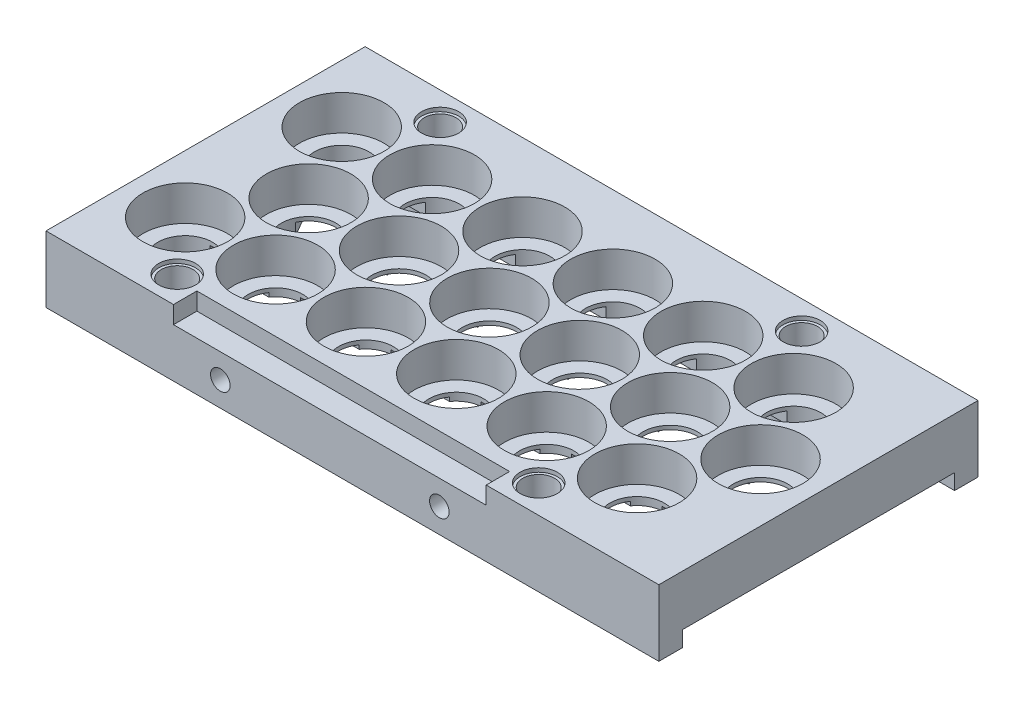
SolidWorks part; units mm, degrees
ref_plane "Front Plane" through (0, 0, 0) normal (0, 0, 1) x (1, 0, 0)
ref_plane "Top Plane" through (0, 0, 0) normal (0, 1, 0) x (1, 0, 0)
ref_plane "Right Plane" through (0, 0, 0) normal (1, 0, 0) x (0, 0, -1)
sketch "Sketch1" plane through (0, 0, 0) normal (0, 1, 0) x (1, 0, 0)
  line L0 (0, 0) -> (11.575, -20.0485) construction
  line L1 (11.575, -20.0485) -> (0, -40.097) construction
  line L2 (0, 0) -> (11.575, 0) construction
  line L3 (11.575, 0) -> (11.575, -20.0485) construction
  line L4 (11.575, -20.0485) -> (11.575, -40.097) construction
  line L5 (11.575, -40.097) -> (0, -40.097) construction
  line L6 (0, 0) -> (23.15, 0) construction
  line L7 (0, 0) -> (23.15, 0) construction
  line L8 (-14.825, -60.922) -> (142.15, -60.922)
  line L9 (-14.825, -60.922) -> (-14.825, 20.825)
  line L10 (-14.825, 20.825) -> (142.15, 20.825)
  line L11 (142.15, -60.922) -> (142.15, 20.825)
  circle A0 centre (0, 0) radius 10.825
  circle A1 centre (11.575, -20.0485) radius 10.825
  circle A2 centre (0, -40.097) radius 10.825
  circle A3 centre (23.15, 0) radius 10.825
  circle A4 centre (34.725, -20.0485) radius 10.825
  circle A5 centre (23.15, -40.097) radius 10.825
  circle A6 centre (46.3, 0) radius 10.825
  circle A7 centre (57.875, -20.0485) radius 10.825
  circle A8 centre (46.3, -40.097) radius 10.825
  circle A9 centre (69.45, 0) radius 10.825
  circle A10 centre (81.025, -20.0485) radius 10.825
  circle A11 centre (69.45, -40.097) radius 10.825
  circle A12 centre (92.6, 0) radius 10.825
  circle A13 centre (104.175, -20.0485) radius 10.825
  circle A14 centre (92.6, -40.097) radius 10.825
  circle A15 centre (115.75, 0) radius 10.825
  circle A16 centre (127.325, -20.0485) radius 10.825
  circle A17 centre (115.75, -40.097) radius 10.825
  circle A18 centre (0, 0) radius 7
  circle A19 centre (11.575, -20.0485) radius 7
  circle A20 centre (0, -40.097) radius 7
  circle A21 centre (23.15, 0) radius 7
  circle A22 centre (34.725, -20.0485) radius 7
  circle A23 centre (23.15, -40.097) radius 7
  circle A24 centre (46.3, 0) radius 7
  circle A25 centre (57.875, -20.0485) radius 7
  circle A26 centre (46.3, -40.097) radius 7
  circle A27 centre (69.45, 0) radius 7
  circle A28 centre (81.025, -20.0485) radius 7
  circle A29 centre (69.45, -40.097) radius 7
  circle A30 centre (92.6, 0) radius 7
  circle A31 centre (104.175, -20.0485) radius 7
  circle A32 centre (92.6, -40.097) radius 7
  circle A33 centre (115.75, 0) radius 7
  circle A34 centre (127.325, -20.0485) radius 7
  circle A35 centre (115.75, -40.097) radius 7
  dimension "D3" = 21.65
  dimension "D11" = 14
  dimension "D1" = 60
  dimension "D2" = 60
  dimension "D4" = 1.5
  dimension "D6" = 23.15
  dimension "D7" = 4
  dimension "D8" = 4
  dimension "D9" = 10
  dimension "D10" = 10
  dimension "D13" = 23.15
  dimension "D5" = 6
  dimension "D12" = 6
extrude "Boss-Extrude2" add sketch "Sketch1" along normal blind 11 contours L8 L11 L10 L9 A17 A16 A15 A14 A13 A12 A11 A10 A9 A8 A7 A6 A5 A4 A3 A2 A1 A0 region at (-13.0551, 0, 20.0485)
extrude "Boss-Extrude3" add sketch "Sketch1<3>" along normal blind 2 contours A0 A18 | A3 A21 | A6 A24 | A9 A27 | A12 A30 | A15 A33 | A1 A19 | A4 A22 | A7 A25 | A10 A28 | A13 A31 | A16 A34 | A17 A35 | A14 A32 | A11 A29 | A8 A26 | A5 A23 | A2 A20 region at (-10.5188, 0, 0) region at (1.0562, 0, 20.0485) region at (-10.5188, 0, 40.097) region at (12.6312, 0, 0) region at (24.2062, 0, 20.0485) region at (12.6312, 0, 40.097) region at (35.7812, 0, 0) region at (47.3562, 0, 20.0485) region at (35.7812, 0, 40.097) region at (58.9312, 0, 0) region at (70.5062, 0, 20.0485) region at (58.9312, 0, 40.097) region at (82.0812, 0, 0) region at (93.6562, 0, 20.0485) region at (82.0812, 0, 40.097) region at (105.2312, 0, 0) region at (116.8062, 0, 20.0485) region at (105.2312, 0, 40.097)
sketch "Sketch1<3>" plane through (0, 0, 0) normal (0, 1, 0) x (1, 0, 0) same geometry as "Sketch1"
sketch "Sketch2" plane through (0, 0, 0) normal (0, -1, 0) x (1, 0, 0)
  line L0 (0, 40.097) -> (11.575, 20.0485) construction
  line L1 (3.4641, 42.097) -> (15.0391, 22.0485)
  line L2 (-3.4641, 38.097) -> (8.1109, 18.0485)
  line L3 (11.575, 20.0485) -> (0, 0) construction
  line L4 (15.0391, 18.0485) -> (3.4641, -2)
  line L5 (8.1109, 22.0485) -> (-3.4641, 2)
  line L6 (19.6859, 38.097) -> (31.2609, 18.0485)
  line L7 (26.6141, 42.097) -> (38.1891, 22.0485)
  line L8 (31.2609, 22.0485) -> (19.6859, 2)
  line L9 (38.1891, 18.0485) -> (26.6141, -2)
  line L10 (23.15, 40.097) -> (34.725, 20.0485) construction
  line L11 (34.725, 20.0485) -> (23.15, 0) construction
  line L12 (42.8359, 38.097) -> (54.4109, 18.0485)
  line L13 (49.7641, 42.097) -> (61.3391, 22.0485)
  line L14 (54.4109, 22.0485) -> (42.8359, 2)
  line L15 (61.3391, 18.0485) -> (49.7641, -2)
  line L16 (46.3, 40.097) -> (57.875, 20.0485) construction
  line L17 (57.875, 20.0485) -> (46.3, 0) construction
  line L18 (65.9859, 38.097) -> (77.5609, 18.0485)
  line L19 (72.9141, 42.097) -> (84.4891, 22.0485)
  line L20 (77.5609, 22.0485) -> (65.9859, 2)
  line L21 (84.4891, 18.0485) -> (72.9141, -2)
  line L22 (69.45, 40.097) -> (81.025, 20.0485) construction
  line L23 (81.025, 20.0485) -> (69.45, 0) construction
  line L24 (89.1359, 38.097) -> (100.7109, 18.0485)
  line L25 (96.0641, 42.097) -> (107.6391, 22.0485)
  line L26 (100.7109, 22.0485) -> (89.1359, 2)
  line L27 (107.6391, 18.0485) -> (96.0641, -2)
  line L28 (92.6, 40.097) -> (104.175, 20.0485) construction
  line L29 (104.175, 20.0485) -> (92.6, 0) construction
  line L30 (112.2859, 38.097) -> (123.8609, 18.0485)
  line L31 (119.2141, 42.097) -> (130.7891, 22.0485)
  line L32 (123.8609, 22.0485) -> (112.2859, 2)
  line L33 (130.7891, 18.0485) -> (119.2141, -2)
  line L34 (115.75, 40.097) -> (127.325, 20.0485) construction
  line L35 (127.325, 20.0485) -> (115.75, 0) construction
  line L36 (-3.4641, 38.097) -> (19.6859, 38.097) construction
  line L37 (0, 40.097) -> (115.75, 40.097) construction
  line L38 (0, 44.097) -> (115.75, 44.097)
  line L39 (0, 36.097) -> (115.75, 36.097)
  line L40 (11.575, 20.0485) -> (127.325, 20.0485) construction
  line L41 (11.575, 24.0485) -> (127.325, 24.0485)
  line L42 (11.575, 16.0485) -> (127.325, 16.0485)
  line L43 (0, 0) -> (115.75, 0) construction
  line L44 (0, 4) -> (115.75, 4)
  line L45 (0, -4) -> (115.75, -4)
  arc A0 (3.4641, 42.097) -> (-3.4641, 38.097) centre (0, 40.097) ccw
  arc A1 (8.1109, 18.0485) -> (15.0391, 22.0485) centre (11.575, 20.0485) ccw
  arc A2 (15.0391, 18.0485) -> (8.1109, 22.0485) centre (11.575, 20.0485) ccw
  arc A3 (-3.4641, 2) -> (3.4641, -2) centre (0, 0) ccw
  arc A4 (26.6141, 42.097) -> (19.6859, 38.097) centre (23.15, 40.097) ccw
  arc A5 (31.2609, 18.0485) -> (38.1891, 22.0485) centre (34.725, 20.0485) ccw
  arc A6 (38.1891, 18.0485) -> (31.2609, 22.0485) centre (34.725, 20.0485) ccw
  arc A7 (19.6859, 2) -> (26.6141, -2) centre (23.15, 0) ccw
  arc A8 (49.7641, 42.097) -> (42.8359, 38.097) centre (46.3, 40.097) ccw
  arc A9 (54.4109, 18.0485) -> (61.3391, 22.0485) centre (57.875, 20.0485) ccw
  arc A10 (61.3391, 18.0485) -> (54.4109, 22.0485) centre (57.875, 20.0485) ccw
  arc A11 (42.8359, 2) -> (49.7641, -2) centre (46.3, 0) ccw
  arc A12 (72.9141, 42.097) -> (65.9859, 38.097) centre (69.45, 40.097) ccw
  arc A13 (77.5609, 18.0485) -> (84.4891, 22.0485) centre (81.025, 20.0485) ccw
  arc A14 (84.4891, 18.0485) -> (77.5609, 22.0485) centre (81.025, 20.0485) ccw
  arc A15 (65.9859, 2) -> (72.9141, -2) centre (69.45, 0) ccw
  arc A16 (96.0641, 42.097) -> (89.1359, 38.097) centre (92.6, 40.097) ccw
  arc A17 (100.7109, 18.0485) -> (107.6391, 22.0485) centre (104.175, 20.0485) ccw
  arc A18 (107.6391, 18.0485) -> (100.7109, 22.0485) centre (104.175, 20.0485) ccw
  arc A19 (89.1359, 2) -> (96.0641, -2) centre (92.6, 0) ccw
  arc A20 (119.2141, 42.097) -> (112.2859, 38.097) centre (115.75, 40.097) ccw
  arc A21 (123.8609, 18.0485) -> (130.7891, 22.0485) centre (127.325, 20.0485) ccw
  arc A22 (130.7891, 18.0485) -> (123.8609, 22.0485) centre (127.325, 20.0485) ccw
  arc A23 (112.2859, 2) -> (119.2141, -2) centre (115.75, 0) ccw
  arc A24 (0, 44.097) -> (0, 36.097) centre (0, 40.097) ccw
  arc A25 (115.75, 36.097) -> (115.75, 44.097) centre (115.75, 40.097) ccw
  arc A26 (11.575, 24.0485) -> (11.575, 16.0485) centre (11.575, 20.0485) ccw
  arc A27 (127.325, 16.0485) -> (127.325, 24.0485) centre (127.325, 20.0485) ccw
  arc A28 (0, 4) -> (0, -4) centre (0, 0) ccw
  arc A29 (115.75, -4) -> (115.75, 4) centre (115.75, 0) ccw
  point P3 (5.7875, 30.0727)
  point P8 (5.7875, 10.0242)
  point P18 (28.9375, 30.0727)
  point P25 (28.9375, 10.0242)
  point P34 (52.0875, 30.0727)
  point P39 (52.0875, 10.0242)
  point P48 (75.2375, 30.0727)
  point P53 (75.2375, 10.0242)
  point P62 (98.3875, 30.0727)
  point P67 (98.3875, 10.0242)
  point P76 (121.5375, 30.0727)
  point P81 (121.5375, 10.0242)
  point P91 (57.875, 40.097)
  point P96 (69.45, 20.0485)
  point P103 (57.875, 0)
  circle M62 centre (0, 0) radius 7
  circle M63 centre (23.15, 0) radius 7
  circle M64 centre (46.3, 0) radius 7
  circle M65 centre (69.45, 0) radius 7
  circle M66 centre (92.6, 0) radius 7
  circle M67 centre (115.75, 0) radius 7
  circle M68 centre (11.575, 20.0485) radius 7
  circle M69 centre (34.725, 20.0485) radius 7
  circle M70 centre (57.875, 20.0485) radius 7
  circle M71 centre (81.025, 20.0485) radius 7
  circle M72 centre (104.175, 20.0485) radius 7
  circle M73 centre (127.325, 20.0485) radius 7
  circle M74 centre (115.75, 40.097) radius 7
  circle M75 centre (92.6, 40.097) radius 7
  circle M76 centre (69.45, 40.097) radius 7
  circle M77 centre (46.3, 40.097) radius 7
  circle M78 centre (23.15, 40.097) radius 7
  circle M79 centre (0, 40.097) radius 7
  dimension "D1" = 8
  dimension "D3" = 23.15
  dimension "D4" = 8
  dimension "D5" = 8
  dimension "D6" = 8
extrude "Cut-Extrude1" cut sketch "Sketch2" against normal blind 1 contours L1 L39 L38 M78 M79 | L7 L39 L38 M77 M78 | L39 L2 L1 M79 M68 | L42 L8 L6 L41 M68 M69 | L6 L41 L7 L39 M69 M78 | L12 L41 L13 L39 M70 M77 | L13 L39 L38 M76 M77 | L18 L41 L19 L39 M71 M76 | L19 L39 L38 M75 M76 | L24 L41 L25 L39 M72 M75 | L25 L39 L38 M74 M75 | L30 L41 L31 M73 M74 | L42 L32 L30 L41 M72 M73 | L42 L26 L24 L41 M71 M72 | L42 L20 L18 L41 M70 M71 | L42 L14 L12 L41 M69 M70 | L45 L44 L4 M62 M63 | L44 L4 L5 M62 M68 | L45 L44 L9 M63 M64 | L45 L44 L15 M64 M65 | L45 L44 L21 M65 M66 | L45 L44 L27 M66 M67 | L44 L27 L42 L26 M66 M72 | L42 L32 L33 M67 M73 | L44 L21 L42 L20 M65 M71 | L44 L15 L42 L14 M64 M70 | L39 L13 M77 | L39 L25 M75 | L39 L19 M76 | L41 L6 M69 | L44 L4 M62 | L44 L15 M64 | L44 L21 M65 | L44 L27 M66 | L41 L30 M73 | L32 L42 M73 | L41 L24 M72 | L26 L42 M72 | L41 L18 M71 | L20 L42 M71 | L41 L12 M70 | L14 L42 M70 | L44 L9 L42 L8 M63 M69 | L8 L42 M69 | L39 L7 M78 | L39 L1 M79 | L44 A29 L45 A28 region at (11.6138, 0, 40.1242) region at (6.3461, 0, 36.4331) region at (5.7834, 0, 30.0255) region at (23.0718, 0, 20.0485) region at (28.9375, 0, 30.0727) region at (34.7638, 0, 40.1242) region at (28.3789, 0, 23.7124) region at (5.7834, 0, 10.0715) region at (29.4961, 0, 36.4331) region at (57.9138, 0, 40.1242) region at (28.3789, 0, 16.3846) region at (28.9375, 0, 10.0242) region at (6.3461, 0, 3.6639) region at (11.6138, 0, -0.0272) region at (52.0875, 0, 30.0727) region at (46.2218, 0, 20.0485) region at (52.6461, 0, 36.4331) region at (81.0638, 0, 40.1242) region at (51.5289, 0, 23.7124) region at (34.7638, 0, -0.0272) region at (75.2375, 0, 30.0727) region at (75.7961, 0, 36.4331) region at (104.2138, 0, 40.1242) region at (74.6789, 0, 23.7124) region at (69.3718, 0, 20.0485) region at (51.5289, 0, 16.3846) region at (52.0875, 0, 10.0242) region at (57.9138, 0, -0.0272) region at (98.3875, 0, 30.0727) region at (98.9461, 0, 36.4331) region at (97.8289, 0, 23.7124) region at (92.5218, 0, 20.0485) region at (74.6789, 0, 16.3846) region at (52.6461, 0, 3.6639) region at (81.0638, 0, -0.0272) region at (121.5416, 0, 30.12) region at (75.2375, 0, 10.0242) region at (120.9789, 0, 23.7124) region at (115.6718, 0, 20.0485) region at (97.8289, 0, 16.3846) region at (75.7961, 0, 3.6639) region at (104.2138, 0, -0.0272) region at (98.3875, 0, 10.0242) region at (121.5416, 0, 9.977) region at (120.9789, 0, 16.3846) region at (98.9461, 0, 3.6639)
sketch "Sketch9" plane through (0, 11, 0) normal (0, 1, 0) x (1, 0, 0)
  line L0 (11.575, -60.922) -> (11.575, 20.825)
  line L1 (-14.825, 20.825) -> (142.15, 20.825) construction
  line L2 (104.175, 20.825) -> (104.175, -60.922)
  line L3 (-14.825, -60.922) -> (142.15, -60.922) construction
  circle A0 centre (11.575, 13.625) radius 4.0767
  circle A1 centre (11.575, -53.722) radius 4.0767
  circle A2 centre (104.175, -53.722) radius 4.0767
  circle A3 centre (104.175, 13.625) radius 4.0767
  point P0 (11.575, 13.625)
  point P7 (11.575, -20.0485)
  point P15 (104.175, -20.0485)
  point P20 (104.175, 13.625)
  point P21 (104.175, -53.722)
  point P22 (11.575, -53.722)
  dimension "D5" = 8.1534
  dimension "D1" = 7.2
  dimension "D4" = 7.2
extrude "Cut-Extrude3" cut sketch "Sketch9" against normal up to next contours A2 | A1 | A0 | A3
sketch "Sketch10" plane through (0, 11, 0) normal (0, 1, 0) x (1, 0, 0)
  circle A0 centre (11.575, 13.625) radius 4.7625
  circle A1 centre (104.175, 13.625) radius 4.7625
  circle A2 centre (104.175, -53.722) radius 4.7625
  circle A3 centre (11.575, -53.722) radius 4.7625
  dimension "D1" = 9.525
extrude "Cut-Extrude4" cut sketch "Sketch10" against normal blind 1
sketch "Sketch13" plane through (0, 0, 0) normal (0, -1, 0) x (1, 0, 0)
  line L0 (142.15, 60.922) -> (142.15, -20.825) construction
  line L5 (3.575, 53.722) -> (3.575, 60.922)
  line L8 (-14.825, 60.922) -> (142.15, 60.922) construction
  line L9 (3.575, 60.922) -> (19.575, 60.922)
  line L10 (19.575, 60.922) -> (19.575, 53.722)
  line L12 (57.875, 20.0485) -> (57.875, -20.825) construction
  line L13 (-14.825, -20.825) -> (142.15, -20.825) construction
  line L14 (11.575, 20.0485) -> (127.325, 20.0485) construction
  line L16 (96.175, 60.922) -> (96.175, 53.722)
  line L17 (112.175, 60.922) -> (96.175, 60.922)
  line L18 (112.175, 53.722) -> (112.175, 60.922)
  line L19 (-14.825, 60.922) -> (142.15, 60.922)
  line L20 (-14.825, 60.922) -> (-14.825, 54.922)
  line L21 (-14.825, 54.922) -> (142.15, 54.922)
  line L22 (142.15, 60.922) -> (142.15, 54.922)
  line L23 (142.15, -20.825) -> (142.15, -14.825)
  line L24 (-14.825, -14.825) -> (142.15, -14.825)
  line L25 (-14.825, -20.825) -> (-14.825, -14.825)
  line L26 (-14.825, -20.825) -> (142.15, -20.825)
  line L27 (112.175, -13.625) -> (112.175, -20.825)
  line L28 (112.175, -20.825) -> (96.175, -20.825)
  line L29 (96.175, -20.825) -> (96.175, -13.625)
  line L32 (19.575, -20.825) -> (19.575, -13.625)
  line L33 (3.575, -20.825) -> (19.575, -20.825)
  line L34 (3.575, -13.625) -> (3.575, -20.825)
  circle A4 centre (11.575, 53.722) radius 6.5
  circle A5 centre (11.575, 53.722) radius 8
  circle A6 centre (104.175, 53.722) radius 8
  circle A7 centre (104.175, 53.722) radius 6.5
  circle A8 centre (104.175, -13.625) radius 6.5
  circle A9 centre (104.175, -13.625) radius 8
  circle A10 centre (11.575, -13.625) radius 8
  circle A11 centre (11.575, -13.625) radius 6.5
  line M15 (142.15, 60.922) -> (-14.825, 60.922)
  line M16 (-14.825, 60.922) -> (-14.825, -20.825)
  line M17 (-14.825, -20.825) -> (142.15, -20.825)
  line M18 (142.15, -20.825) -> (142.15, 60.922)
  dimension "D1" = 13
  dimension "D2" = 16
  dimension "D3" = 6
extrude "Boss-Extrude7" add sketch "Sketch13" along normal blind 6 contours L21 L5 M16 M15 | A5 L5 L21 M15 | A5 L21 L10 M15 | L10 L21 L16 M15 | L21 A5 L19 A4 | A5 L21 A4 | L21 A6 L16 M15 | L21 A7 A6 L19 | L21 A7 A6 | A6 L21 L18 M15 | L18 L21 M18 M15 | A9 L24 L29 L26 | L28 A9 L24 A8 | A9 L26 L27 L24 | L24 L27 L26 M18 | L32 L26 L29 L24 | L24 A9 A8 | L34 L24 M16 M17 | L26 A10 L24 L34 | L24 A11 A10 | L24 A11 A10 L33 | L24 A10 L26 L32 region at (3.7817, 0, 54.3098) region at (-5.625, 0, 57.922) region at (4.8282, 0, 59.2567) region at (5.2714, 0, 58.3681) region at (18.3218, 0, 59.2567) region at (57.875, 0, 57.922) region at (-5.625, 0, -17.825) region at (97.4282, 0, 59.2567) region at (4.8282, 0, -19.1597) region at (96.3817, 0, 54.3098) region at (97.8714, 0, 58.3681) region at (3.7817, 0, -14.2128) region at (4.4261, 0, -14.9942) region at (110.9218, 0, 59.2567) region at (127.1625, 0, 57.922) region at (18.3218, 0, -19.1597) region at (57.875, 0, -17.825) region at (97.4282, 0, -19.1597) region at (127.1625, 0, -17.825) region at (96.3817, 0, -14.2128) region at (97.0261, 0, -14.9942) region at (110.9218, 0, -19.1597)
sketch "Sketch14" plane through (0, 0, 0) normal (0, -1, 0) x (1, 0, 0)
  line L2 (142.15, 54.922) -> (142.15, -14.825) construction
  line L4 (5.2386, 17.0736) -> (-0.5918, 6.9749) construction
  line L5 (5.7446, -4) -> (17.4054, -4) construction
  line L6 (28.8946, -4) -> (40.5554, -4) construction
  line L7 (52.0446, -4) -> (63.7054, -4) construction
  line L8 (75.1946, -4) -> (86.8554, -4) construction
  line L9 (98.3446, -4) -> (110.0054, -4) construction
  line L10 (127.9168, 13.0736) -> (122.0864, 2.9749) construction
  line L11 (122.0864, 37.122) -> (127.9168, 27.0234) construction
  line L12 (98.3446, 44.097) -> (110.0054, 44.097) construction
  line L13 (75.1946, 44.097) -> (86.8554, 44.097) construction
  line L14 (52.0446, 44.097) -> (63.7054, 44.097) construction
  line L15 (28.8946, 44.097) -> (40.5554, 44.097) construction
  line L16 (-0.5918, 33.122) -> (5.2386, 23.0234) construction
  line L17 (5.7446, 44.097) -> (17.4054, 44.097) construction
  line L20 (142.15, 54.922) -> (142.15, -14.825)
  line L22 (5.2386, 17.0736) -> (-0.5918, 6.9749)
  line L23 (5.7446, -4) -> (17.4054, -4)
  line L24 (28.8946, -4) -> (40.5554, -4)
  line L25 (52.0446, -4) -> (63.7054, -4)
  line L26 (75.1946, -4) -> (86.8554, -4)
  line L27 (98.3446, -4) -> (110.0054, -4)
  line L28 (127.9168, 13.0736) -> (122.0864, 2.9749)
  line L29 (122.0864, 37.122) -> (127.9168, 27.0234)
  line L30 (98.3446, 44.097) -> (110.0054, 44.097)
  line L31 (75.1946, 44.097) -> (86.8554, 44.097)
  line L32 (52.0446, 44.097) -> (63.7054, 44.097)
  line L33 (28.8946, 44.097) -> (40.5554, 44.097)
  line L34 (-0.5918, 33.122) -> (5.2386, 23.0234)
  line L35 (5.7446, 44.097) -> (17.4054, 44.097)
  line L36 (112.0845, -14.825) -> (142.15, -14.825) construction
  line L37 (19.4845, -14.825) -> (96.2655, -14.825) construction
  line L38 (-14.825, -14.825) -> (3.6655, -14.825) construction
  line L39 (-14.825, 54.922) -> (-14.825, -14.825) construction
  line L40 (112.0845, 54.922) -> (142.15, 54.922) construction
  line L41 (19.4845, 54.922) -> (96.2655, 54.922) construction
  line L42 (-14.825, 54.922) -> (3.6655, 54.922) construction
  line L43 (112.0845, -14.825) -> (142.15, -14.825)
  line L44 (19.4845, -14.825) -> (96.2655, -14.825)
  line L45 (-14.825, -14.825) -> (3.6655, -14.825)
  line L46 (-14.825, 54.922) -> (-14.825, -14.825)
  line L47 (112.0845, 54.922) -> (142.15, 54.922)
  line L48 (19.4845, 54.922) -> (96.2655, 54.922)
  line L49 (-14.825, 54.922) -> (3.6655, 54.922)
  arc A3 (5.2386, 23.0234) -> (5.2386, 17.0736) centre (11.575, 20.0485) ccw construction
  arc A4 (-0.5918, 6.9749) -> (5.7446, -4) centre (0, 0) ccw construction
  arc A5 (17.4054, -4) -> (28.8946, -4) centre (23.15, 0) ccw construction
  arc A6 (40.5554, -4) -> (52.0446, -4) centre (46.3, 0) ccw construction
  arc A7 (63.7054, -4) -> (75.1946, -4) centre (69.45, 0) ccw construction
  arc A8 (86.8554, -4) -> (98.3446, -4) centre (92.6, 0) ccw construction
  arc A9 (110.0054, -4) -> (122.0864, 2.9749) centre (115.75, 0) ccw construction
  arc A10 (127.9168, 13.0736) -> (127.9168, 27.0234) centre (127.325, 20.0485) ccw construction
  arc A11 (122.0864, 37.122) -> (110.0054, 44.097) centre (115.75, 40.097) ccw construction
  arc A12 (98.3446, 44.097) -> (86.8554, 44.097) centre (92.6, 40.097) ccw construction
  arc A13 (75.1946, 44.097) -> (63.7054, 44.097) centre (69.45, 40.097) ccw construction
  arc A14 (52.0446, 44.097) -> (40.5554, 44.097) centre (46.3, 40.097) ccw construction
  arc A16 (28.8946, 44.097) -> (17.4054, 44.097) centre (23.15, 40.097) ccw construction
  arc A17 (5.7446, 44.097) -> (-0.5918, 33.122) centre (0, 40.097) ccw construction
  arc A21 (5.2386, 23.0234) -> (5.2386, 17.0736) centre (11.575, 20.0485) ccw
  arc A22 (-0.5918, 6.9749) -> (5.7446, -4) centre (0, 0) ccw
  arc A23 (17.4054, -4) -> (28.8946, -4) centre (23.15, 0) ccw
  arc A24 (40.5554, -4) -> (52.0446, -4) centre (46.3, 0) ccw
  arc A25 (63.7054, -4) -> (75.1946, -4) centre (69.45, 0) ccw
  arc A26 (86.8554, -4) -> (98.3446, -4) centre (92.6, 0) ccw
  arc A27 (110.0054, -4) -> (122.0864, 2.9749) centre (115.75, 0) ccw
  arc A28 (127.9168, 13.0736) -> (127.9168, 27.0234) centre (127.325, 20.0485) ccw
  arc A29 (122.0864, 37.122) -> (110.0054, 44.097) centre (115.75, 40.097) ccw
  arc A30 (98.3446, 44.097) -> (86.8554, 44.097) centre (92.6, 40.097) ccw
  arc A31 (75.1946, 44.097) -> (63.7054, 44.097) centre (69.45, 40.097) ccw
  arc A32 (52.0446, 44.097) -> (40.5554, 44.097) centre (46.3, 40.097) ccw
  arc A34 (28.8946, 44.097) -> (17.4054, 44.097) centre (23.15, 40.097) ccw
  arc A35 (5.7446, 44.097) -> (-0.5918, 33.122) centre (0, 40.097) ccw
  arc A36 (112.0845, -14.825) -> (96.2655, -14.825) centre (104.175, -13.625) ccw construction
  arc A37 (19.4845, -14.825) -> (3.6655, -14.825) centre (11.575, -13.625) ccw construction
  arc A38 (96.2655, 54.922) -> (112.0845, 54.922) centre (104.175, 53.722) ccw construction
  arc A39 (3.6655, 54.922) -> (19.4845, 54.922) centre (11.575, 53.722) ccw construction
  arc A40 (112.0845, -14.825) -> (96.2655, -14.825) centre (104.175, -13.625) ccw
  arc A41 (19.4845, -14.825) -> (3.6655, -14.825) centre (11.575, -13.625) ccw
  arc A42 (96.2655, 54.922) -> (112.0845, 54.922) centre (104.175, 53.722) ccw
  arc A43 (3.6655, 54.922) -> (19.4845, 54.922) centre (11.575, 53.722) ccw
extrude "Boss-Extrude9" add sketch "Sketch14" along normal blind 2
sketch "Sketch16" plane through (0, 0, 0) normal (0, -1, 0) x (1, 0, 0)
  line L0 (17.4054, 36.097) -> (12.1668, 27.0234) construction
  line L1 (12.1668, 27.0234) -> (17.3196, 24.0485) construction
  line L2 (17.3196, 24.0485) -> (22.5582, 33.122) construction
  line L3 (22.5582, 33.122) -> (17.4054, 36.097) construction
  line L4 (14.7861, 31.5602) -> (19.9389, 28.5853) construction
  line L5 (15.5361, 32.8592) -> (20.6889, 29.8843)
  line L6 (14.0361, 30.2612) -> (19.1889, 27.2862)
  line L7 (11.575, 20.0485) -> (126.446, 20.0485) construction
  line L8 (40.5554, 36.097) -> (35.3168, 27.0234) construction
  line L9 (35.3168, 27.0234) -> (40.4696, 24.0485) construction
  line L10 (40.4696, 24.0485) -> (45.7082, 33.122) construction
  line L11 (45.7082, 33.122) -> (40.5554, 36.097) construction
  line L12 (37.9361, 31.5602) -> (43.0889, 28.5853) construction
  line L13 (38.6861, 32.8592) -> (43.8389, 29.8843)
  line L14 (37.1861, 30.2612) -> (42.3389, 27.2862)
  line L15 (63.7054, 36.097) -> (58.4668, 27.0234) construction
  line L16 (58.4668, 27.0234) -> (63.6196, 24.0485) construction
  line L17 (63.6196, 24.0485) -> (68.8582, 33.122) construction
  line L18 (68.8582, 33.122) -> (63.7054, 36.097) construction
  line L19 (61.0861, 31.5602) -> (66.2389, 28.5853) construction
  line L20 (61.8361, 32.8592) -> (66.9889, 29.8843)
  line L21 (60.3361, 30.2612) -> (65.4889, 27.2862)
  line L22 (86.8554, 36.097) -> (81.6168, 27.0234) construction
  line L23 (81.6168, 27.0234) -> (86.7696, 24.0485) construction
  line L24 (86.7696, 24.0485) -> (92.0082, 33.122) construction
  line L25 (92.0082, 33.122) -> (86.8554, 36.097) construction
  line L26 (84.2361, 31.5602) -> (89.3889, 28.5853) construction
  line L27 (84.9861, 32.8592) -> (90.1389, 29.8843)
  line L28 (83.4861, 30.2612) -> (88.6389, 27.2862)
  line L29 (110.0054, 36.097) -> (104.7668, 27.0234) construction
  line L30 (104.7668, 27.0234) -> (109.9196, 24.0485) construction
  line L31 (109.9196, 24.0485) -> (115.1582, 33.122) construction
  line L32 (115.1582, 33.122) -> (110.0054, 36.097) construction
  line L33 (107.3861, 31.5602) -> (112.5389, 28.5853) construction
  line L34 (108.1361, 32.8592) -> (113.2889, 29.8843)
  line L35 (106.6361, 30.2612) -> (111.7889, 27.2862)
  line L36 (14.7861, 8.5368) -> (19.9389, 11.5117) construction
  line L37 (15.5361, 7.2377) -> (20.6889, 10.2127)
  line L38 (14.0361, 9.8358) -> (19.1889, 12.8108)
  line L39 (37.9361, 8.5368) -> (43.0889, 11.5117) construction
  line L40 (38.6861, 7.2377) -> (43.8389, 10.2127)
  line L41 (37.1861, 9.8358) -> (42.3389, 12.8108)
  line L42 (61.0861, 8.5368) -> (66.2389, 11.5117) construction
  line L43 (61.8361, 7.2377) -> (66.9889, 10.2127)
  line L44 (60.3361, 9.8358) -> (65.4889, 12.8108)
  line L45 (84.2361, 8.5368) -> (89.3889, 11.5117) construction
  line L46 (84.9861, 7.2377) -> (90.1389, 10.2127)
  line L47 (83.4861, 9.8358) -> (88.6389, 12.8108)
  line L48 (107.3861, 8.5368) -> (112.5389, 11.5117) construction
  line L49 (108.1361, 7.2377) -> (113.2889, 10.2127)
  line L50 (106.6361, 9.8358) -> (111.7889, 12.8108)
  line L51 (115.1582, 6.9749) -> (110.0054, 4) construction
  line L52 (109.9196, 16.0485) -> (115.1582, 6.9749) construction
  line L53 (104.7668, 13.0736) -> (109.9196, 16.0485) construction
  line L54 (110.0054, 4) -> (104.7668, 13.0736) construction
  line L55 (92.0082, 6.9749) -> (86.8554, 4) construction
  line L56 (86.7696, 16.0485) -> (92.0082, 6.9749) construction
  line L57 (81.6168, 13.0736) -> (86.7696, 16.0485) construction
  line L58 (86.8554, 4) -> (81.6168, 13.0736) construction
  line L59 (68.8582, 6.9749) -> (63.7054, 4) construction
  line L60 (63.6196, 16.0485) -> (68.8582, 6.9749) construction
  line L61 (58.4668, 13.0736) -> (63.6196, 16.0485) construction
  line L62 (63.7054, 4) -> (58.4668, 13.0736) construction
  line L63 (45.7082, 6.9749) -> (40.5554, 4) construction
  line L64 (40.4696, 16.0485) -> (45.7082, 6.9749) construction
  line L65 (35.3168, 13.0736) -> (40.4696, 16.0485) construction
  line L66 (40.5554, 4) -> (35.3168, 13.0736) construction
  line L67 (22.5582, 6.9749) -> (17.4054, 4) construction
  line L68 (17.3196, 16.0485) -> (22.5582, 6.9749) construction
  line L69 (12.1668, 13.0736) -> (17.3196, 16.0485) construction
  line L70 (17.4054, 4) -> (12.1668, 13.0736) construction
  arc A0 (15.5361, 32.8592) -> (14.0361, 30.2612) centre (14.7861, 31.5602) ccw
  arc A1 (19.1889, 27.2862) -> (20.6889, 29.8843) centre (19.9389, 28.5853) ccw
  arc A2 (38.6861, 32.8592) -> (37.1861, 30.2612) centre (37.9361, 31.5602) ccw
  arc A3 (42.3389, 27.2862) -> (43.8389, 29.8843) centre (43.0889, 28.5853) ccw
  arc A4 (61.8361, 32.8592) -> (60.3361, 30.2612) centre (61.0861, 31.5602) ccw
  arc A5 (65.4889, 27.2862) -> (66.9889, 29.8843) centre (66.2389, 28.5853) ccw
  arc A6 (84.9861, 32.8592) -> (83.4861, 30.2612) centre (84.2361, 31.5602) ccw
  arc A7 (88.6389, 27.2862) -> (90.1389, 29.8843) centre (89.3889, 28.5853) ccw
  arc A8 (108.1361, 32.8592) -> (106.6361, 30.2612) centre (107.3861, 31.5602) ccw
  arc A9 (111.7889, 27.2862) -> (113.2889, 29.8843) centre (112.5389, 28.5853) ccw
  arc A10 (40.5554, 36.097) -> (45.7082, 33.122) centre (46.3, 40.097) ccw construction
  arc A11 (15.5361, 7.2377) -> (14.0361, 9.8358) centre (14.7861, 8.5368) cw
  arc A12 (19.1889, 12.8108) -> (20.6889, 10.2127) centre (19.9389, 11.5117) cw
  arc A13 (38.6861, 7.2377) -> (37.1861, 9.8358) centre (37.9361, 8.5368) cw
  arc A14 (42.3389, 12.8108) -> (43.8389, 10.2127) centre (43.0889, 11.5117) cw
  arc A15 (61.8361, 7.2377) -> (60.3361, 9.8358) centre (61.0861, 8.5368) cw
  arc A16 (65.4889, 12.8108) -> (66.9889, 10.2127) centre (66.2389, 11.5117) cw
  arc A17 (84.9861, 7.2377) -> (83.4861, 9.8358) centre (84.2361, 8.5368) cw
  arc A18 (88.6389, 12.8108) -> (90.1389, 10.2127) centre (89.3889, 11.5117) cw
  arc A19 (108.1361, 7.2377) -> (106.6361, 9.8358) centre (107.3861, 8.5368) cw
  arc A20 (111.7889, 12.8108) -> (113.2889, 10.2127) centre (112.5389, 11.5117) cw
  point P10 (17.3625, 30.0727)
  point P25 (40.5125, 30.0727)
  point P36 (63.6625, 30.0727)
  point P47 (86.8125, 30.0727)
  point P58 (109.9625, 30.0727)
  point P68 (17.3625, 10.0242)
  point P75 (40.5125, 10.0242)
  point P82 (63.6625, 10.0242)
  point P89 (86.8125, 10.0242)
  point P96 (109.9625, 10.0242)
  dimension "D1" = 1.5
  dimension "D2" = 5
extrude "Boss-Extrude10" add sketch "Sketch16" along normal blind 2
sketch "Sketch17" plane through (0, -2, 0) normal (0, -1, 0) x (-1, 0, 0)
  line L0 (-57.875, -44.097) -> (-57.875, -54.922) construction
  line L1 (-63.7054, -44.097) -> (-52.0446, -44.097) construction
  line L2 (-19.4845, -54.922) -> (-96.2655, -54.922) construction
  line L3 (-142.15, 14.825) -> (-142.15, -54.922) construction
  line L4 (14.825, -54.922) -> (14.825, 14.825) construction
  line L5 (10.825, -49.5095) -> (-57.875, -49.5095) construction
  line L6 (-57.875, -49.5095) -> (-132.15, -49.5095) construction
  line L7 (-127.325, -20.0485) -> (-11.575, -20.0485)
  line L8 (-57.875, 9.4125) -> (-132.15, 9.4125) construction
  line L9 (10.825, 9.4125) -> (-57.875, 9.4125) construction
  line L10 (-57.875, 4) -> (-57.875, 14.825) construction
  circle A0 centre (10.825, -49.5095) radius 2.5
  circle A1 centre (-57.875, -49.5095) radius 2.5
  circle A2 centre (-132.15, -49.5095) radius 2.5
  circle A3 centre (-132.15, 9.4125) radius 2.5
  circle A4 centre (-57.875, 9.4125) radius 2.5
  circle A5 centre (10.825, 9.4125) radius 2.5
  dimension "D1" = 5
  dimension "D2" = 10
  dimension "D3" = 4
extrude "Cut-Extrude5" cut sketch "Sketch17" against normal blind 4 contours A3 | A2 | A4 | A5 | A0 | A1 region at (-10.825, -2, 49.5095) region at (57.875, -2, 49.5095) region at (132.15, -2, 49.5095) region at (132.15, -2, -9.4125) region at (57.875, -2, -9.4125) region at (-10.825, -2, -9.4125)
sketch "Sketch19" plane through (0, 0, 60.922) normal (0, 0, 1) x (1, 0, 0)
  line L0 (11.575, 11) -> (104.175, 11)
  line L1 (-14.825, 11) -> (142.15, 11) construction
  line L2 (97.925, 11) -> (17.825, 11)
  line L3 (17.825, 11) -> (97.925, 11)
  line L4 (17.825, 11) -> (17.825, 6.525)
  line L5 (97.925, 11) -> (97.925, 6.525)
  line L6 (17.825, 6.525) -> (97.925, 6.525)
  point P5 (57.875, 11)
  point P9 (57.875, 11)
  dimension "D1" = 92.6
  dimension "D2" = 26.4
  dimension "D3" = 80.1
  dimension "D4" = 4.475
extrude "Cut-Extrude6" cut sketch "Sketch19" against normal blind 6 contours L4 L6 L5 L0 region at (57.875, 8.7625, 60.922)
sketch "Sketch20" plane through (0, 0, 60.922) normal (0, 0, 1) x (1, 0, 0)
  line L0 (29.825, 6.525) -> (85.925, 6.525)
  line L1 (29.825, 6.525) -> (29.825, 0.2625)
  line L2 (85.925, 6.525) -> (85.925, 0.2625)
  line L3 (29.825, 0.2625) -> (85.925, 0.2625)
  line L4 (29.825, 6.525) -> (17.825, 6.525) construction
  line L5 (85.925, 6.525) -> (97.925, 6.525) construction
  line L6 (57.875, 6.525) -> (57.875, -6)
  line L9 (142.15, -6) -> (-14.825, -6) construction
  circle A0 centre (29.825, 0.2625) radius 2.5
  circle A1 centre (85.925, 0.2625) radius 2.5
  point P9 (57.875, 0.2625)
  point P11 (0, 0)
  point P13 (0, 0)
  point P14 (0, 0)
  point P15 (58.67, 0.2625)
  point P16 (0, 0)
  point P19 (88.8082, 6.525)
  point P20 (0, 0)
  dimension "D2" = 5
  dimension "D1" = 12
extrude "Cut-Extrude7" cut sketch "Sketch20" against normal blind 5 contours L1 A0 L3 | L3 A0 L1 | L3 A1 L2 | L2 A1 L3 region at (30.886, 1.3235, 60.922) region at (29.4713, -0.0912, 60.922) region at (86.2787, -0.0912, 60.922) region at (84.864, 1.3235, 60.922)
equation "\"hole_diameter\"= 21.65"
equation "\"D3@Sketch1\"=\"hole_diameter\""
equation "\"cell_spacing\"= 1.5"
equation "\"D4@Sketch1\"=\"cell_spacing\""
equation "\"D6@Sketch1\"=\"hole_diameter\"+\"cell_spacing\""
equation "\"len_spacing\"= 4"
equation "\"D7@Sketch1\"=\"len_spacing\""
equation "\"D8@Sketch1\"=\"len_spacing\""
equation "\"wid_spacing\"= 10"
equation "\"D9@Sketch1\"=\"wid_spacing\""
equation "\"D10@Sketch1\"=\"wid_spacing\""
equation "\"nipple\"= 14"
equation "\"D11@Sketch1\"=\"nipple\""
equation "\"D13@Sketch1\"=\"hole_diameter\"+\"cell_spacing\""
equation "\"channel\"= 8"
equation "\"D1@Sketch2\"=\"channel\""
equation "\"D3@Sketch2\"=\"hole_diameter\"+\"cell_spacing\""
equation "\"D4@Sketch2\"=\"channel\""
equation "\"D5@Sketch2\"=\"channel\""
equation "\"D6@Sketch2\"=\"channel\""
equation "\"lip\"= 6"
equation "\"lip_height\"= 1"
equation "\"outer_fillet\"=6"
equation "\"insert_placement\"= 7.2"
equation "\"D4@Sketch9\"=\"insert_placement\""
equation "\"D1@Sketch9\"=\"insert_placement\""
equation "\"heat_insert_diameter\"=8.1534"
equation "\"D5@Sketch9\"=\"heat_insert_diameter\""
equation "\"heat_insert_lip_diameter\"=9.525"
equation "\"D1@Sketch10\"=\"heat_insert_lip_diameter\""
equation "\"bolt_head_diameter\"=13"
equation "\"D1@Sketch13\"=\"bolt_head_diameter\""
equation "\"D2@Sketch13\"=\"bolt_head_diameter\"+3"
equation "\"D3@Sketch13\"=\"lip\""
equation "\"small_heat_insert\"=5"
equation "\"D1@Sketch17\"=\"small_heat_insert\""
equation "\"bdm_cut_depth\"=6"
equation "\"D1@Cut-Extrude6\"=\"bdm_cut_depth\""
equation "\"D1@Cut-Extrude7\"=\"small_heat_insert\""
equation "\"D2@Sketch20\"=\"small_heat_insert\""
equation "\"heat_insert_space\"=6"
equation "\"heat_insert\"=5.5"
